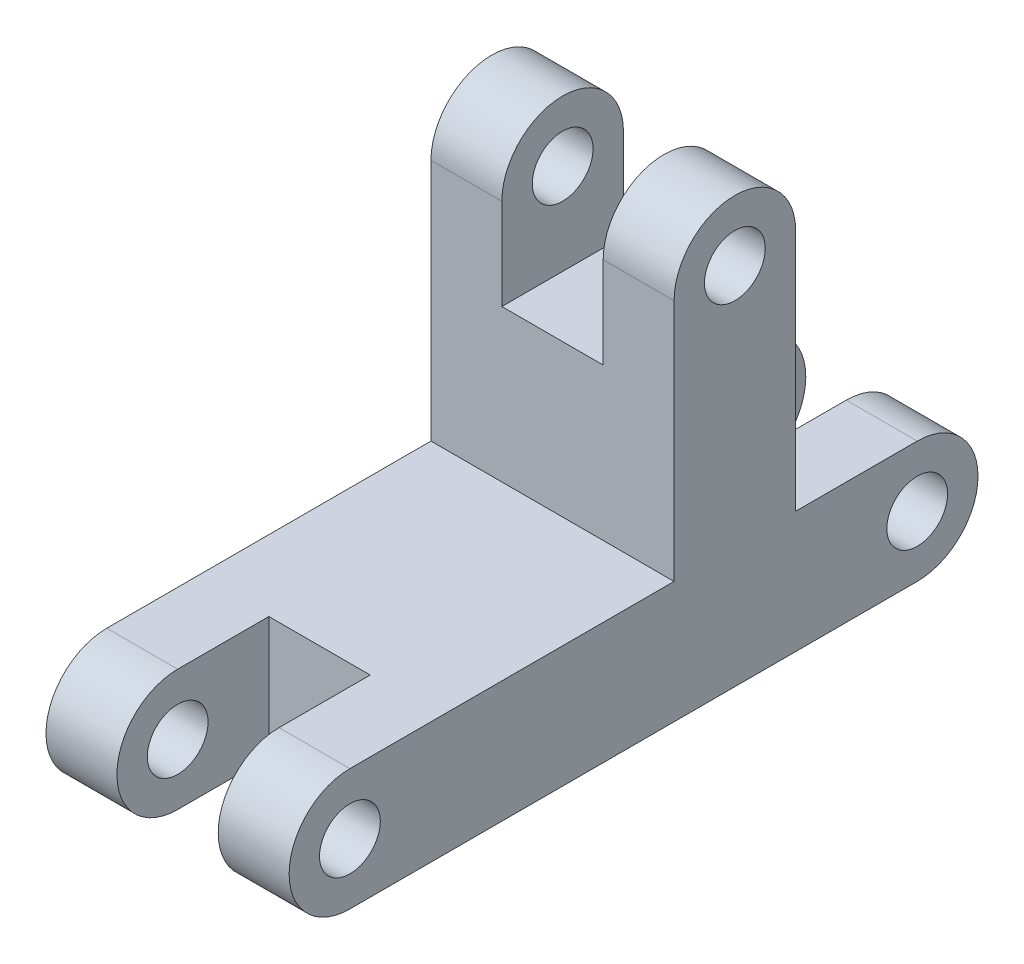
SolidWorks part; units mm, degrees
ref_plane "Alzado" through (0, 0, 0) normal (0, 0, 1) x (1, 0, 0)
ref_plane "Planta" through (0, 0, 0) normal (0, 1, 0) x (1, 0, 0)
ref_plane "Vista lateral" through (0, 0, 0) normal (1, 0, 0) x (0, 0, -1)
sketch "Croquis1" plane through (0, 0, 0) normal (1, 0, 0) x (0, 0, -1)
  line L0 (-14, 0) -> (14, 0) construction
  line L1 (-14, 3) -> (2, 3)
  line L2 (-14, -3) -> (14, -3)
  line L3 (8, 3) -> (14, 3)
  line L5 (2, 3) -> (2, 15)
  line L6 (2, 15) -> (8, 15) construction
  line L7 (8, 3) -> (8, 15)
  arc A0 (-14, 3) -> (-14, -3) centre (-14, 0) ccw
  arc A1 (14, -3) -> (14, 3) centre (14, 0) ccw
  circle A2 centre (14, 0) radius 1.5
  arc A3 (8, 15) -> (2, 15) centre (5, 15) ccw
  circle A4 centre (5, 15) radius 1.5
  circle A5 centre (-14, 0) radius 1.5
  point P3 (0, 0)
  dimension "D2" = 3
  dimension "D3" = 3
  dimension "D4" = 3
  dimension "D1" = 28
  dimension "D5" = 6
  dimension "D6" = 12
extrude "Saliente-Extruir1" add sketch "Croquis1" along normal mid plane 12
sketch "Croquis2" plane through (0, 0, 0) normal (1, 0, 0) x (0, 0, -1)
  line L0 (2, 15) -> (2, 3) construction
  line L1 (2, 10.5) -> (8, 10.5)
  line L2 (2, 10.5) -> (2, 18)
  line L3 (2, 18) -> (8, 18)
  line L4 (8, 10.5) -> (8, 18)
  line L5 (8, 3) -> (8, 15) construction
  line L6 (2, 3) -> (-14, 3) construction
  line L7 (-9.5, 3) -> (-17, 3)
  line L8 (-9.5, 3) -> (-9.5, -3)
  line L9 (-9.5, -3) -> (-17, -3)
  line L10 (-17, 3) -> (-17, -3)
  line L11 (-14, -3) -> (14, -3) construction
  line L12 (14, 3) -> (8, 3) construction
  line L13 (9.5, 3) -> (17, 3)
  line L14 (9.5, 3) -> (9.5, -3)
  line L15 (9.5, -3) -> (17, -3)
  line L16 (17, 3) -> (17, -3)
  arc A0 (8, 15) -> (2, 15) centre (5, 15) ccw construction
  arc A1 (-14, 3) -> (-14, -3) centre (-14, 0) ccw construction
  arc A2 (14, -3) -> (14, 3) centre (14, 0) ccw construction
  dimension "D1" = 7.5
  dimension "D2" = 7.5
  dimension "D3" = 7.5
extrude "Cortar-Extruir1" cut sketch "Croquis2" against normal mid plane 5
